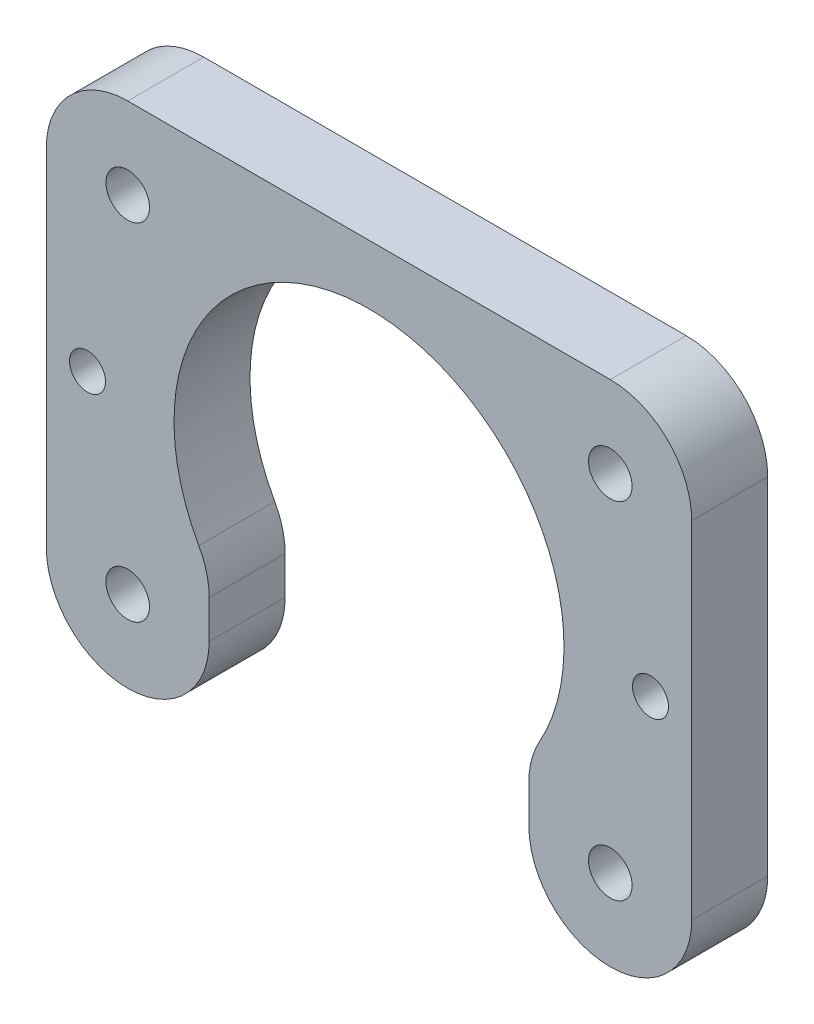
SolidWorks part; units mm, degrees
material "Balsa"
ref_plane "Front" through (0, 0, 0) normal (0, 0, 1) x (1, 0, 0)
ref_plane "Top" through (0, 0, 0) normal (0, 1, 0) x (1, 0, 0)
ref_plane "Right" through (0, 0, 0) normal (1, 0, 0) x (0, 0, -1)
sketch "Sketch1" plane through (0, 0, 0) normal (0, 0, 1) x (1, 0, 0)
  line L0 (50.8, 20) -> (0, 20)
  line L1 (0, 20) -> (0, -20)
  line L2 (0, -20) -> (50.8, -20)
  line L3 (25.4, 0) -> (25.4, 20) construction
  line L4 (50.8, 20) -> (50.8, -20)
  line L5 (0, 0) -> (25.4, 0) construction
  circle A0 centre (25.4, 0) radius 20 construction
  point P9 (25.4, -20)
  dimension "D1" = 40
  dimension "D2" = 40
  dimension "D3" = 25.4
extrude "Boss-Extrude1" add sketch "Sketch1" along normal blind 6
sketch "Sketch10" plane through (0, 0, 6) normal (0, 0, 1) x (1, 0, 0)
  line L0 (25.4, 20) -> (25.4, -20) construction
  line L1 (50.8, 20) -> (0, 20) construction
  line L2 (0, -20) -> (50.8, -20) construction
  line L3 (50.8, -20) -> (50.8, 20) construction
  line L4 (25.4, 0) -> (50.8, 0) construction
  circle A0 centre (44.45, 13.65) radius 1.8
  circle A1 centre (44.45, -13.65) radius 1.8
  circle A2 centre (6.35, -13.65) radius 1.8
  circle A3 centre (6.35, 13.65) radius 1.8
  dimension "D3" = 3.6
  dimension "D1" = 6.35
  dimension "D2" = 6.35
extrude "M3-through" cut sketch "Sketch10" against normal through all
sketch "Sketch9" plane through (0, 0, 6) normal (0, 0, 1) x (1, 0, 0)
  line L0 (0, 0) -> (50.8, 0) construction
  line L1 (50.8, -20) -> (50.8, 20) construction
  line L2 (12.7, -8.8423) -> (12.7, -20)
  line L3 (0, 20) -> (0, -20) construction
  line L4 (12.7, -20) -> (38.1, -20)
  line L5 (38.1, -20) -> (38.1, -8.8423)
  line L6 (0, -20) -> (50.8, -20) construction
  arc A0 (38.1, -8.8423) -> (12.7, -8.8423) centre (25.4, 0) ccw
  dimension "D1" = 15.475
  dimension "D2" = 12.7
extrude "Cut-Extrude2" cut sketch "Sketch9" against normal through all
fillet "Fillet1" radius 6.35 8 edges at (0, -20, 3) (50.8, -20, 3) (50.8, 20, 3) (0, 20, 3) (38.1, -20, 3) (38.1, -8.8423, 3) (12.7, -8.8423, 3) (12.7, -20, 3)
sketch "Sketch8" plane through (0, 0, 6) normal (0, 0, 1) x (1, 0, 0)
  line L0 (0, 0) -> (50.8, 0) construction
  line L1 (25.4, 0) -> (25.4, -22.225) construction
  line L3 (0, 13.65) -> (0, -13.65) construction
  line L6 (50.8, -13.65) -> (50.8, 13.65) construction
  line L7 (25.4, 0) -> (25.4, 20) construction
  line L8 (44.45, 20) -> (6.35, 20) construction
  circle A0 centre (47.625, 0) radius 1.5
  circle A2 centre (3.175, 0) radius 1.5
  circle A4 centre (25.4, 22.225) radius 1.5 [skipped]
  circle A5 centre (25.4, -22.225) radius 1.5 [skipped]
  dimension "D2" = 3
  dimension "D1" = 22.225
  dimension "D3" = 4
extrude "Cut-Extrude1" cut sketch "Sketch8" against normal through all
other "Move Face1" face at (2.5174, -17.4826, 3) face at (10.1826, -17.4826, 3) face at (12.7, -12.1501, 3) face at (12.3956, -9.075, 3) face at (38.4044, -9.075, 3) face at (25.4, 3.9617, 3) face at (38.1, -12.1501, 3) face at (40.6174, -17.4826, 3) face at (48.2826, -17.4826, 3) face at (50.8, 0, 3) face at (48.2826, 17.4826, 3) face at (2.5174, 17.4826, 3) face at (4.55, 13.65, 0) face at (46.25, 13.65, 0) face at (42.65, -13.65, 0) face at (8.15, -13.65, 0) face at (49.125, 0, 0) face at (4.675, 0, 0) face at (25.4, 20, 3) face at (0, 0, 3) offset 0.08 parameters "D1"=0.08
